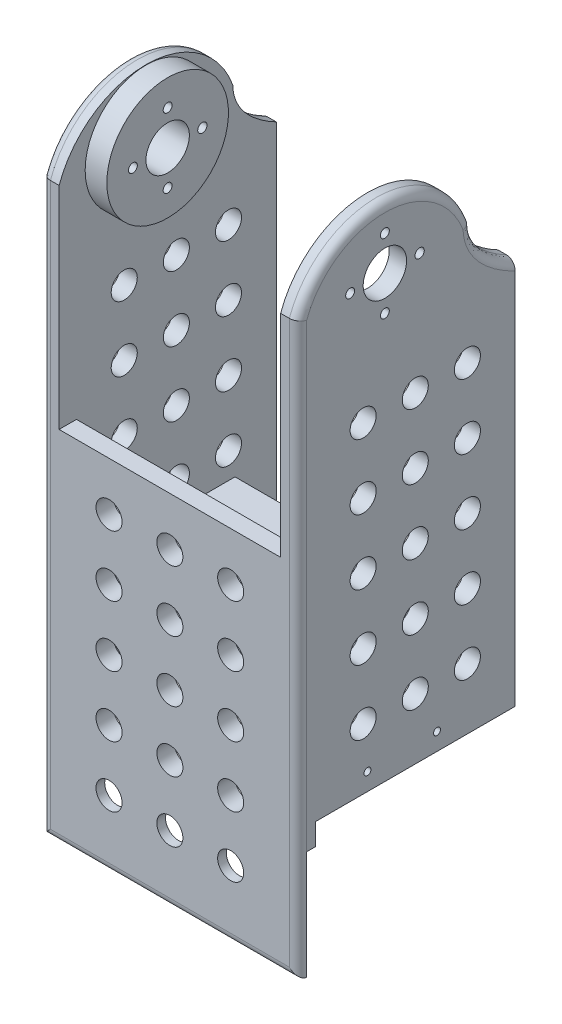
SolidWorks part; units mm, degrees
material "ABS"
ref_plane "Front Plane" through (0, 0, 0) normal (0, 0, 1) x (1, 0, 0)
ref_plane "Top Plane" through (0, 0, 0) normal (0, 1, 0) x (1, 0, 0)
ref_plane "Right Plane" through (0, 0, 0) normal (1, 0, 0) x (0, 0, -1)
sketch "Sketch5" plane through (0, 0, 0) normal (0, 1, 0) x (1, 0, 0)
  line L1 (-29.5, -40) -> (29.5, -40)
  line L2 (-29.5, -40) -> (-29.5, 40)
  line L3 (-29.5, 40) -> (29.5, 40)
  line L4 (29.5, -40) -> (29.5, 40)
  line L5 (-29.5, -40) -> (29.5, 40) construction
  line L6 (-29.5, 40) -> (29.5, -40) construction
  point P0 (0, 0)
  dimension "D1" = 59
  dimension "D2" = 80
extrude "Boss-Extrude3" add sketch "Sketch5" along normal mid plane 82.71
shell "Shell2" thickness 4 removed face at (0, -41.355, 0) removed face at (0, 0, -40) removed face at (0, 41.355, 0)
sketch "Sketch6" plane through (-29.5, 0, 0) normal (-1, 0, 0) x (0, 0, 1)
  line L0 (40, 60) -> (40, 41.355)
  line L1 (40, 41.355) -> (-40, 41.355)
  arc A0 (40, 60) -> (0, 60) centre (20, 52.8483) ccw
  circle A1 centre (20, 60) radius 5
  ellipse E0 centre (-40, 60) end of major axis (0, 60) minor radius 18.645 (-40, 41.355) -> (0, 60) ccw
  dimension "D2" = 10
extrude "Boss-Extrude4" add sketch "Sketch6" against normal blind 4
mirror "Mirror7" about plane through (0, 0, 0) normal (1, 0, 0) of "Boss-Extrude4"
sketch "Sketch8" plane through (29.5, 0, 0) normal (1, 0, 0) x (0, 0, -1)
  line L0 (-40, -41.355) -> (40, -41.355) construction
  line L1 (-40, 60) -> (-40, -41.355) construction
  circle A0 centre (-24, -37.355) radius 0.8
  circle A1 centre (-8, -37.355) radius 0.8
  dimension "D1" = 1.6
  dimension "D2" = 1.6
  dimension "D3" = 4
  dimension "D4" = 4
  dimension "D5" = 16
  dimension "D6" = 16
extrude "Cut-Extrude1" cut sketch "Sketch8" against normal through all both and the other way through all
sketch "Sketch9" plane through (-25.5, 0, 0) normal (1, 0, 0) x (0, 0, -1)
  line L0 (-20, 60) -> (-20, 52) construction
  line L1 (-20, 60) -> (-20, 68) construction
  line L2 (-20, 60) -> (-28, 60) construction
  line L3 (-20, 60) -> (-12, 60) construction
  circle A0 centre (-20, 52) radius 1.025
  circle A1 centre (-28, 60) radius 1.025
  circle A2 centre (-20, 68) radius 1.025
  circle A3 centre (-12, 60) radius 1.025
extrude "Cut-Extrude2" cut sketch "Sketch9" along normal through all both and the other way through all
sketch "Sketch10" plane through (0, 41.355, 0) normal (0, 1, 0) x (1, 0, 0)
  line L1 (25.5, -40) -> (-25.5, -40)
  line L2 (25.5, -40) -> (25.5, -36)
  line L3 (25.5, -36) -> (-25.5, -36)
  line L4 (-25.5, -40) -> (-25.5, -36)
extrude "Cut-Extrude3" cut sketch "Sketch10" against normal blind 30
sketch "Sketch11" plane through (-25.5, 0, 0) normal (1, 0, 0) x (0, 0, -1)
  circle A0 centre (-20, 60) radius 14
  circle A1 centre (-20, 60) radius 5
extrude "Boss-Extrude6" add sketch "Sketch11" along normal blind 7.07
sketch "Sketch12" plane through (-29.5, 0, 0) normal (-1, 0, 0) x (0, 0, 1)
  circle A0 centre (20, 52) radius 1.025
  circle A1 centre (12, 60) radius 1.0713
  circle A2 centre (20, 68) radius 1.025
  circle A3 centre (28, 60) radius 1.025
extrude "Cut-Extrude4" cut sketch "Sketch12" against normal through all both and the other way through all
sketch "Sketch13" plane through (0, 0, -40) normal (0, 0, -1) x (-1, 0, 0)
  line L1 (48.077, 66.1185) -> (-48.077, 66.1185)
  line L2 (48.077, 66.1185) -> (48.077, -66.1185)
  line L3 (48.077, -66.1185) -> (-48.077, -66.1185)
  line L4 (-48.077, 66.1185) -> (-48.077, -66.1185)
  line L5 (48.077, 66.1185) -> (-48.077, -66.1185) construction
  line L6 (48.077, -66.1185) -> (-48.077, 66.1185) construction
  point P0 (0, 0)
extrude "Cut-Extrude5" cut sketch "Sketch13" against normal blind 30
sketch "Sketch15" plane through (0, 0, 36) normal (0, 0, -1) x (-1, 0, 0)
  line L0 (25.5, 11.355) -> (25.5, -41.355) construction
  line L1 (25.5, -22.355) -> (-25.5, -22.355)
  line L2 (25.5, -22.355) -> (25.5, -18.355)
  line L3 (25.5, -18.355) -> (-25.5, -18.355)
  line L4 (-25.5, -22.355) -> (-25.5, -18.355)
  line L5 (-25.5, 11.355) -> (-25.5, -41.355) construction
  line L6 (25.5, -41.355) -> (-25.5, -41.355) construction
  dimension "D1" = 4
  dimension "D2" = 19
extrude "Boss-Extrude7" add sketch "Sketch15" along normal blind 36.5
sketch "Sketch16" plane through (0, -22.355, 0) normal (0, -1, 0) x (1, 0, 0)
  line L0 (25.5, -0.5) -> (-25.5, -0.5) construction
  line L1 (-25.5, -0.5) -> (-25.5, 36) construction
  circle A0 centre (0, 5) radius 1.25
  circle A1 centre (0, 27) radius 1.25
  circle A2 centre (-11, 16) radius 1.25
  circle A3 centre (11, 16) radius 1.25
  dimension "D1" = 5.5
  dimension "D4" = 22
  dimension "D5" = 11
  dimension "D2" = 5.5
  dimension "D3" = 25.5
  dimension "D6" = 11
  dimension "D7" = 11
  dimension "D8" = 11
extrude "Cut-Extrude6" cut sketch "Sketch16" against normal through all
sketch "Sketch17" plane through (0, -41.355, 0) normal (0, -1, 0) x (1, 0, 0)
  line L0 (-29.5, -10) -> (-29.5, 40) construction
  line L1 (29.5, 40) -> (-29.5, 40)
  line L2 (29.5, 40) -> (29.5, 36)
  line L3 (29.5, 36) -> (-29.5, 36)
  line L4 (-29.5, 40) -> (-29.5, 36)
  dimension "D1" = 4
extrude "Boss-Extrude8" add sketch "Sketch17" along normal blind 30
fillet "Fillet2" radius 2 7 edges at (-29.5, 53.408, -2.5834) (29.5, 53.408, -2.5834) (29.5, 74.0885, 20) (-29.5, 74.0885, 20) (0, -71.355, 40) (-29.5, -5.6775, 40) (29.5, -5.6775, 40)
sketch "Sketch18" plane through (0, 0, 40) normal (0, 0, 1) x (1, 0, 0)
  line L0 (27.5, -69.355) -> (27.5, 60) construction
  line L1 (-27.5, -69.355) -> (27.5, -69.355) construction
  circle A0 centre (14, -55.855) radius 3
  dimension "D1" = 13.5
  dimension "D2" = 13.5
extrude "Cut-Extrude7" cut sketch "Sketch18" against normal blind 4
pattern_linear "LPattern1" count 3 spacing 14 along (-1, 0, 0) count 5 spacing 14 along (0, 1, 0) of "Cut-Extrude7"
sketch "Sketch19" plane through (29.5, 0, 0) normal (1, 0, 0) x (0, 0, -1)
  line L0 (10, -41.355) -> (10, 45.4214) construction
  line L2 (-36, -41.355) -> (10, -41.355) construction
  circle A0 centre (-1, -27.355) radius 3
  dimension "D1" = 11
  dimension "D2" = 14
extrude "Cut-Extrude8" cut sketch "Sketch19" against normal through all
pattern_linear "LPattern2" count 3 spacing 12 along (0, 0, 1) count 5 spacing 15 along (0, 1, 0) of "Cut-Extrude8"
sketch "Sketch20" plane through (-18.43, 0, 0) normal (1, 0, 0) x (0, 0, -1)
  circle A0 centre (-20, 60) radius 14
extrude "Cut-Extrude9" cut sketch "Sketch20" against normal blind 2.08
sketch "Sketch21" plane through (0, 0, 36) normal (0, 0, -1) x (-1, 0, 0)
  line L0 (-29.5, -71.355) -> (-29.5, -41.355) construction
  line L1 (29.5, -71.355) -> (-29.5, -71.355)
  line L2 (29.5, -71.355) -> (29.5, -46.355)
  line L3 (29.5, -46.355) -> (-29.5, -46.355)
  line L4 (-29.5, -71.355) -> (-29.5, -46.355)
  dimension "D1" = 25
extrude "Cut-Extrude11" cut sketch "Sketch21" against normal blind 2
